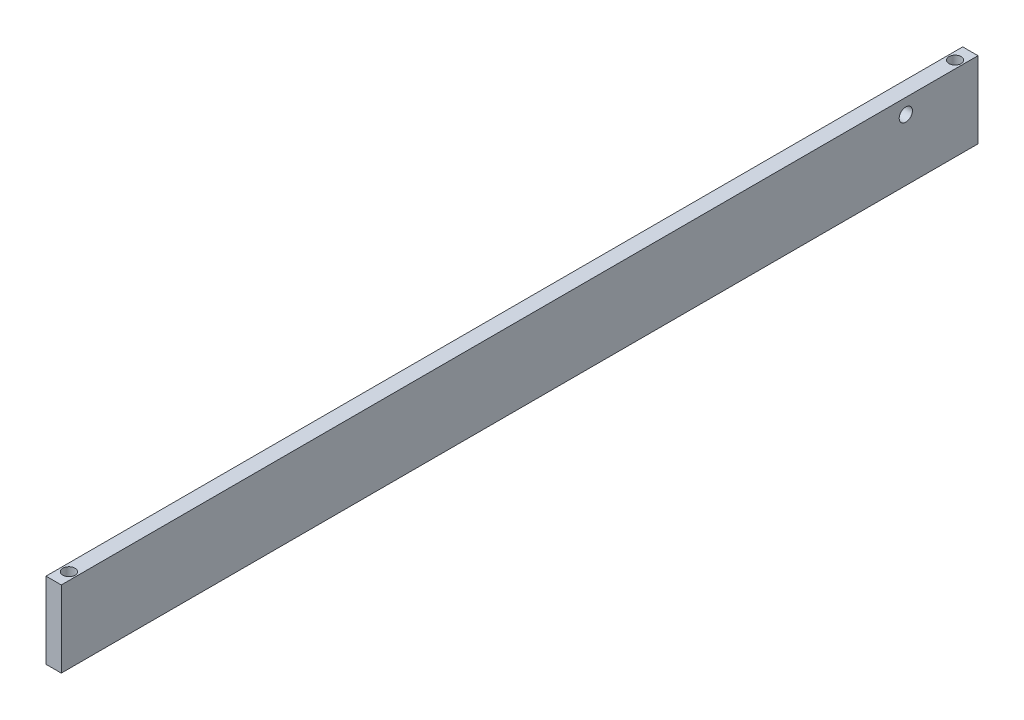
SolidWorks part; units mm, degrees
other "Markup1"
sketch "Sketch6" plane through (0, 0, 0) normal (0.7258, -0.6292, 0.2781) x (-0.261, -0.6259, -0.735)
ref_plane "Front Plane" through (0, 0, 0) normal (0, 0, 1) x (1, 0, 0)
ref_plane "Top Plane" through (0, 0, 0) normal (0, 1, 0) x (1, 0, 0)
ref_plane "Right Plane" through (0, 0, 0) normal (1, 0, 0) x (0, 0, -1)
sketch "Sketch1" plane through (0, 0, 0) normal (0, 0, 1) x (1, 0, 0)
  line L1 (-6.35, 0) -> (-6.35, 31.75)
  line L2 (-6.35, 31.75) -> (0, 31.75)
  line L3 (0, 31.75) -> (0, 0)
  line L6 (-6.35, 0) -> (0, 0)
  point P0 (0, 0)
  dimension "D3" = 6.35
  dimension "D4" = 31.75
extrude "Boss-Extrude1" add sketch "Sketch1" against normal blind 381
sketch "Sketch2" plane through (-6.35, 0, 0) normal (-1, 0, 0) x (0, 0, 1)
  circle A8 centre (-351, 25.5625) radius 2.75
  circle A9 centre (-351, 25.5625) radius 2.75
  dimension "D7" = 0
extrude "Cut-Extrude1" cut sketch "Sketch2" against normal up to next
sketch "Sketch3" plane through (0, 31.75, 0) normal (0, 1, 0) x (1, 0, 0)
  line L0 (-3.175, 381) -> (-3.175, 0) construction
  line L1 (0, 381) -> (-6.35, 381) construction
  line L2 (0, 0) -> (-6.35, 0) construction
  circle A0 centre (-3.175, 6.35) radius 2.54
  circle A1 centre (-3.175, 374.65) radius 2.54
  dimension "D1" = 5.08
  dimension "D3" = 6.35
  dimension "D2" = 6.35
extrude "Cut-Extrude2" cut sketch "Sketch3" against normal blind 7.62
sketch "Sketch4" plane through (0, 0, 0) normal (0, -1, 0) x (1, 0, 0)
  line L0 (-9.525, 0) -> (-9.525, -381) construction
  line L1 (-12.7, 0) -> (0, 0) construction
  line L2 (-12.7, -381) -> (0, -381) construction
  line L3 (0, -381) -> (0, 0) construction
  circle A0 centre (-9.525, -374.65) radius 2.54
  circle A1 centre (-9.525, -6.35) radius 2.54
  dimension "D2" = 5.08
  dimension "D1" = 9.525
  dimension "D3" = 6.35
  dimension "D4" = 6.35
sketch "Sketch5" plane through (0, 0, -381) normal (0, 0, -1) x (-1, 0, 0)
  line L1 (6.35, 6.35) -> (0, 6.35)
  line L2 (6.35, 6.35) -> (6.35, 0)
  line L3 (6.35, 0) -> (0, 0)
  line L4 (0, 6.35) -> (0, 0)
